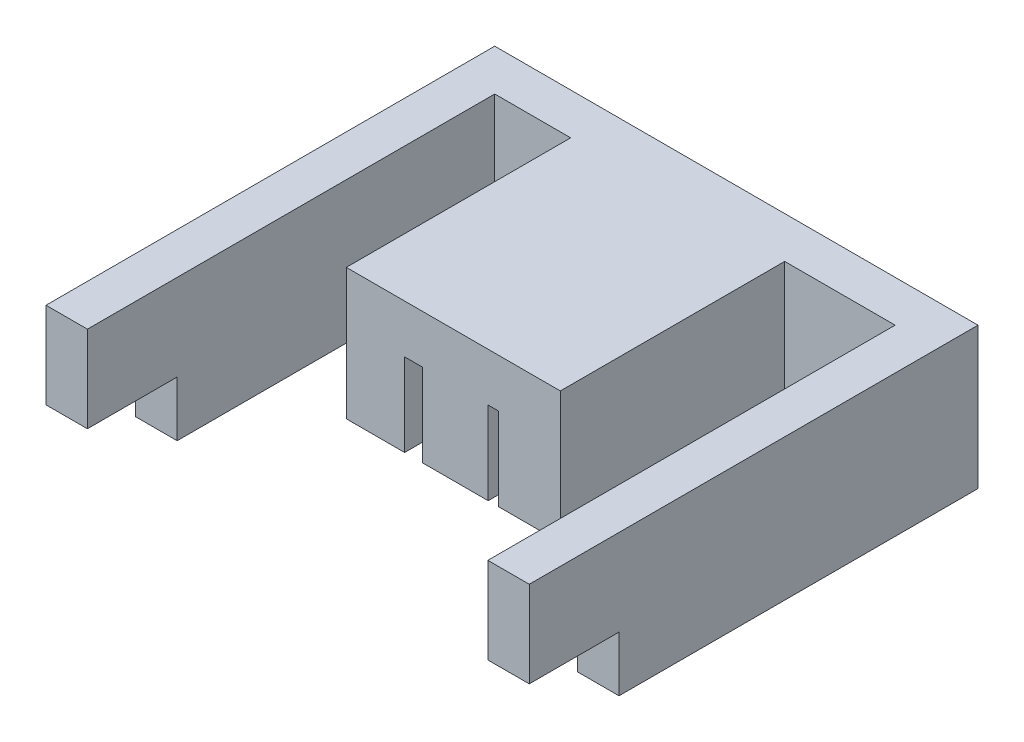
SolidWorks part; units mm, degrees
material "PBT General Purpose"
ref_plane "Front Plane" through (0, 0, 0) normal (0, 0, 1) x (1, 0, 0)
ref_plane "Top Plane" through (0, 0, 0) normal (0, 1, 0) x (1, 0, 0)
ref_plane "Right Plane" through (0, 0, 0) normal (1, 0, 0) x (0, 0, -1)
sketch "Sketch1" plane through (0, 0, 0) normal (0, 1, 0) x (1, 0, 0)
  line L0 (29, -32.5) -> (35, -32.5)
  line L1 (-35, 32.5) -> (35, 32.5)
  line L2 (-35, 32.5) -> (-35, -32.5)
  line L3 (-35, -32.5) -> (-29, -32.5)
  line L4 (35, 32.5) -> (35, -32.5)
  line L5 (-29, 26.5) -> (29, 26.5)
  line L6 (-29, 26.5) -> (-29, -32.5)
  line L8 (29, 26.5) -> (29, -32.5)
  point P8 (0, 26.5)
  point P10 (-35, 0)
  dimension "D1" = 70
  dimension "D2" = 65
  dimension "D3" = 6
  dimension "D4" = 6
  dimension "D5" = 6
extrude "Boss-Extrude1" add sketch "Sketch1" along normal blind 20.5
sketch "Sketch2" plane through (0, 0, 0) normal (0, -1, 0) x (1, 0, 0)
  line L0 (35, 32.5) -> (35, -32.5) construction
  line L1 (29, 32.5) -> (35, 32.5)
  line L2 (29, 32.5) -> (29, 19.5)
  line L3 (29, 19.5) -> (35, 19.5)
  line L4 (35, 32.5) -> (35, 19.5)
  line L5 (0, -1000) -> (0, 49000) construction
  line L6 (-29, -26.5) -> (29, -26.5) construction
  line L7 (-12.5, -26.5) -> (12.5, -26.5)
  line L8 (-12.5, -26.5) -> (-12.5, -32.5)
  line L9 (-12.5, -32.5) -> (12.5, -32.5)
  line L10 (12.5, -26.5) -> (12.5, -32.5)
  line L11 (35, -32.5) -> (-35, -32.5) construction
  line L12 (-29, 19.5) -> (-35, 19.5)
  line L13 (-35, 32.5) -> (-35, 19.5)
  line L14 (-29, 32.5) -> (-35, 32.5)
  line L15 (-29, 32.5) -> (-29, 19.5)
  point P18 (0, -26.5)
  point P19 (0, -26.5)
  dimension "D1" = 13
  dimension "D2" = 25
extrude "Cut-Extrude1" cut sketch "Sketch2" against normal blind 8
sketch "Sketch3" plane through (0, 20.5, 0) normal (0, 1, 0) x (1, 0, 0)
  line L0 (-29, -32.5) -> (-29, 26.5) construction
  line L1 (-14, 21) -> (9, 21)
  line L2 (-14, 21) -> (-14, -2)
  line L3 (-14, -2) -> (9, -2)
  line L4 (9, 21) -> (9, -2)
  line L5 (-29, 26.5) -> (29, 26.5) construction
  dimension "D1" = 23
  dimension "D2" = 23
  dimension "D3" = 15
  dimension "D4" = 5.5
extrude "Boss-Extrude2" add sketch "Sketch3" against normal offset from surface (7 mm away) 13.5 separate body up to face at (-25.5, 0, -13.1667)
sketch "Sketch4" plane through (0, 20.5, 0) normal (0, 1, 0) x (1, 0, 0)
  line L0 (-18, 26.5) -> (-18, -6)
  line L1 (-29, 26.5) -> (29, 26.5) construction
  line L2 (-18, -6) -> (13, -6)
  line L3 (13, -6) -> (13, 26.5)
  line L4 (-14, 21) -> (-14, -2)
  line L5 (-14, -2) -> (9, -2)
  line L6 (9, -2) -> (9, 21)
  line L7 (9, 21) -> (-14, 21)
  line L8 (-14, 21) -> (-14, -2)
  line L9 (-14, -2) -> (9, -2)
  line L10 (9, -2) -> (9, 21)
  line L11 (9, 21) -> (-14, 21)
  line L12 (13, 26.5) -> (-18, 26.5)
  line M12 (-29, 26.5) -> (29, 26.5)
  dimension "D2" = 4
  dimension "D3" = 4
  dimension "D4" = 4
  dimension "D1" = 0
extrude "Boss-Extrude4" add sketch "Sketch4" against normal offset from surface (19 mm away) 12 contours L2 L3 L0 L11 L10 L9 L8 M12 region at (-2.5, 20.5, -26.0509) up to face at (-2.5, 13.5, -9.5) offset beyond the face yes
sketch "Sketch5" plane through (0, 1.5, 0) normal (0, -1, 0) x (1, 0, 0)
  line L0 (-14, -21) -> (9, -21) construction
  line L1 (-6.95, -21) -> (-9.55, -21)
  line L2 (-6.95, -21) -> (-6.95, -26.5)
  line L3 (-6.95, -26.5) -> (-9.55, -26.5)
  line L4 (-9.55, -21) -> (-9.55, -26.5)
  line L5 (12.5, -26.5) -> (-12.5, -26.5) construction
  line L6 (9, 2) -> (-14, 2) construction
  line L7 (-9.55, 2) -> (-6.95, 2)
  line L8 (-9.55, 2) -> (-9.55, 6)
  line L9 (-9.55, 6) -> (-6.95, 6)
  line L10 (-6.95, 2) -> (-6.95, 6)
  line L11 (13, 6) -> (-18, 6) construction
  line L12 (-18, 6) -> (-18, -26.5) construction
  line L13 (-18, 2) -> (-14, 2)
  line L14 (-18, 2) -> (-18, -13)
  line L15 (-18, -13) -> (-14, -13)
  line L16 (-14, 2) -> (-14, -13)
  line L17 (-14, 2) -> (-14, -21) construction
  line L18 (9, 2) -> (-14, 2) construction
  line L19 (2.55, 6) -> (4.05, 6)
  line L20 (2.55, 6) -> (2.55, 2)
  line L21 (2.55, 2) -> (4.05, 2)
  line L22 (4.05, 6) -> (4.05, 2)
  line L23 (-14, 2) -> (-14, -21) construction
  dimension "D1" = 1.5
  dimension "D2" = 9.5
  dimension "D3" = 15
  dimension "D4" = 2.6
  dimension "D5" = 4.45
extrude "Cut-Extrude2" cut sketch "Sketch5" against normal up to surface (12 mm away) up to face at (-2.5, 13.5, -9.5)
sketch "Sketch6" plane through (0, 0, 0) normal (0, -1, 0) x (1, 0, 0)
  line L1 (-35, 19.5) -> (-29, 19.5) construction
  line L2 (-29, -26.5) -> (-12.5, -26.5) construction
  circle A0 centre (-32, 14.5) radius 1.5
  circle A1 centre (-32, -21.5) radius 1.5
  point P6 (-32, 19.5)
  point P7 (0, 0)
  dimension "D1" = 3
  dimension "D3" = 3
  dimension "D2" = 5
  dimension "D4" = 5
extrude "Cut-Extrude3" cut sketch "Sketch6" against normal blind 10
mirror "Mirror1" about plane through (0, 0, 0) normal (1, 0, 0) of "Cut-Extrude3"
equation "\"body_height\"= 41mm"
equation "\"D1@Boss-Extrude1\"=\"body_height\" / 2"
equation "\"D1@Boss-Extrude2\"=12+1.5"
